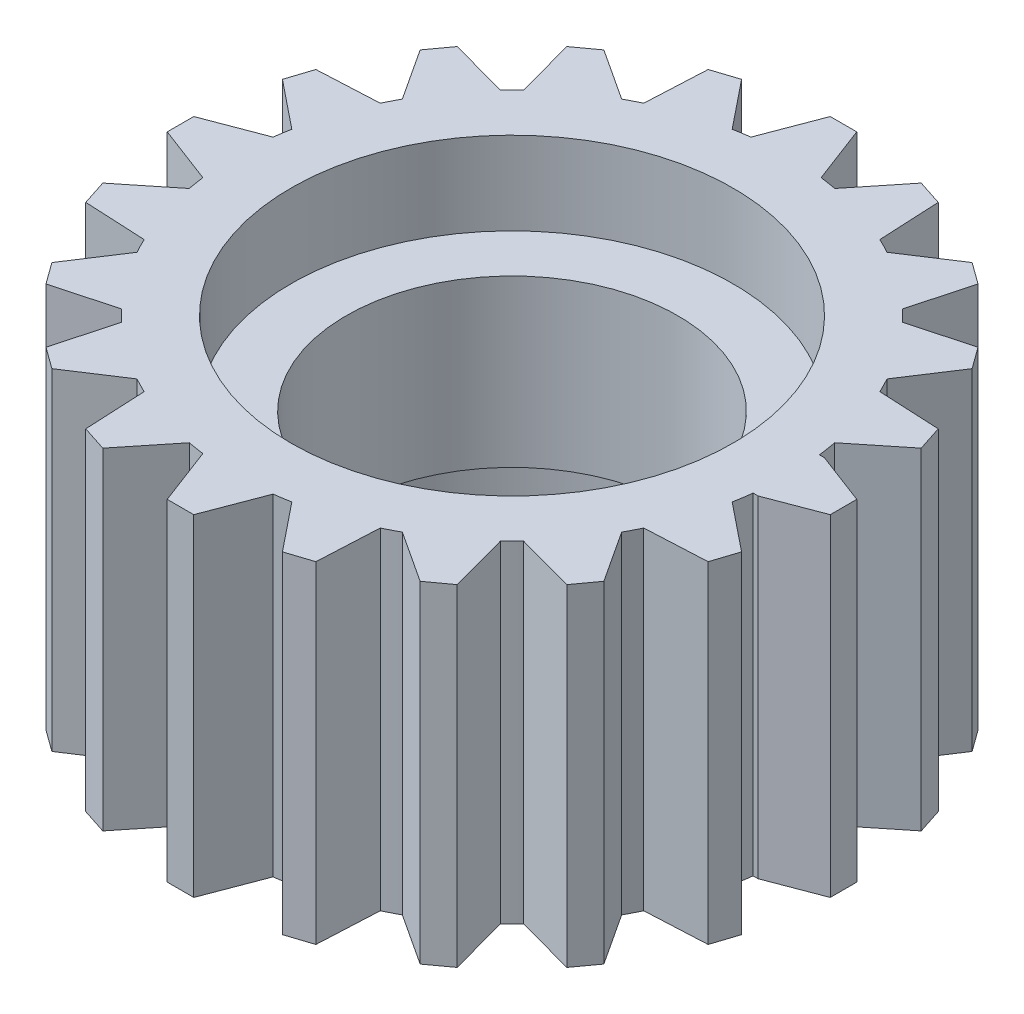
SolidWorks part; units mm, degrees
ref_plane "Front Plane" through (0, 0, 0) normal (0, 0, 1) x (1, 0, 0)
ref_plane "Top Plane" through (0, 0, 0) normal (0, 1, 0) x (1, 0, 0)
ref_plane "Right Plane" through (0, 0, 0) normal (1, 0, 0) x (0, 0, -1)
sketch "Sketch2" plane through (0, 0, 0) normal (0, 1, 0) x (1, 0, 0)
  line L0 (0, 0) -> (39.7409, 0) construction
  line L2 (0, 35.6097) -> (0, 0) construction
  line L3 (0, -3) -> (39.7409, -3)
  line L4 (0, 3) -> (39.7409, 3)
  line L5 (30, 1.2) -> (30, -1.2)
  line L6 (30, -1.2) -> (24.7972, -3.1775)
  line L7 (30, 1.2) -> (24.7972, 3.1775)
  line L8 (28.9025, -8.1292) -> (24.5655, -4.6408)
  line L9 (28.1609, -10.4118) -> (22.6017, -10.6848)
  line L10 (28.9025, -8.1292) -> (28.1609, -10.4118)
  line L11 (24.9759, -16.6627) -> (21.9291, -12.0048)
  line L12 (23.5652, -18.6044) -> (18.1937, -17.1461)
  line L13 (24.9759, -16.6627) -> (23.5652, -18.6044)
  line L14 (18.6044, -23.5652) -> (17.1461, -18.1937)
  line L15 (16.6627, -24.9759) -> (12.0048, -21.9291)
  line L16 (18.6044, -23.5652) -> (16.6627, -24.9759)
  line L17 (10.4118, -28.1609) -> (10.6848, -22.6017)
  line L18 (8.1292, -28.9025) -> (4.6408, -24.5655)
  line L19 (10.4118, -28.1609) -> (8.1292, -28.9025)
  line L20 (1.2, -30) -> (3.1775, -24.7972)
  line L21 (-1.2, -30) -> (-3.1775, -24.7972)
  line L22 (1.2, -30) -> (-1.2, -30)
  line L23 (-8.1292, -28.9025) -> (-4.6408, -24.5655)
  line L24 (-10.4118, -28.1609) -> (-10.6848, -22.6017)
  line L25 (-8.1292, -28.9025) -> (-10.4118, -28.1609)
  line L26 (-16.6627, -24.9759) -> (-12.0048, -21.9291)
  line L27 (-18.6044, -23.5652) -> (-17.1461, -18.1937)
  line L28 (-16.6627, -24.9759) -> (-18.6044, -23.5652)
  line L29 (-23.5652, -18.6044) -> (-18.1937, -17.1461)
  line L30 (-24.9759, -16.6627) -> (-21.9291, -12.0048)
  line L31 (-23.5652, -18.6044) -> (-24.9759, -16.6627)
  line L32 (-28.1609, -10.4118) -> (-22.6017, -10.6848)
  line L33 (-28.9025, -8.1292) -> (-24.5655, -4.6408)
  line L34 (-28.1609, -10.4118) -> (-28.9025, -8.1292)
  line L35 (-30, -1.2) -> (-24.7972, -3.1775)
  line L36 (-30, 1.2) -> (-24.7972, 3.1775)
  line L37 (-30, -1.2) -> (-30, 1.2)
  line L38 (-28.9025, 8.1292) -> (-24.5655, 4.6408)
  line L39 (-28.1609, 10.4118) -> (-22.6017, 10.6848)
  line L40 (-28.9025, 8.1292) -> (-28.1609, 10.4118)
  line L41 (-24.9759, 16.6627) -> (-21.9291, 12.0048)
  line L42 (-23.5652, 18.6044) -> (-18.1937, 17.1461)
  line L43 (-24.9759, 16.6627) -> (-23.5652, 18.6044)
  line L44 (-18.6044, 23.5652) -> (-17.1461, 18.1937)
  line L45 (-16.6627, 24.9759) -> (-12.0048, 21.9291)
  line L46 (-18.6044, 23.5652) -> (-16.6627, 24.9759)
  line L47 (-10.4118, 28.1609) -> (-10.6848, 22.6017)
  line L48 (-8.1292, 28.9025) -> (-4.6408, 24.5655)
  line L49 (-10.4118, 28.1609) -> (-8.1292, 28.9025)
  line L50 (-1.2, 30) -> (-3.1775, 24.7972)
  line L51 (1.2, 30) -> (3.1775, 24.7972)
  line L52 (-1.2, 30) -> (1.2, 30)
  line L53 (8.1292, 28.9025) -> (4.6408, 24.5655)
  line L54 (10.4118, 28.1609) -> (10.6848, 22.6017)
  line L55 (8.1292, 28.9025) -> (10.4118, 28.1609)
  line L56 (16.6627, 24.9759) -> (12.0048, 21.9291)
  line L57 (18.6044, 23.5652) -> (17.1461, 18.1937)
  line L58 (16.6627, 24.9759) -> (18.6044, 23.5652)
  line L59 (23.5652, 18.6044) -> (18.1937, 17.1461)
  line L60 (24.9759, 16.6627) -> (21.9291, 12.0048)
  line L61 (23.5652, 18.6044) -> (24.9759, 16.6627)
  line L62 (28.1609, 10.4118) -> (22.6017, 10.6848)
  line L63 (28.9025, 8.1292) -> (24.5655, 4.6408)
  line L64 (28.1609, 10.4118) -> (28.9025, 8.1292)
  circle A0 centre (0, 0) radius 15
  circle A1 centre (0, 0) radius 20
  circle A3 centre (0, 0) radius 25
  point P16 (30, 0)
  point P17 (0, 0)
  point P94 (0, 0)
  dimension "D1" = 3
  dimension "D3" = 20
  dimension "D2" = 6
extrude "Boss-Extrude1" add sketch "Sketch2" along normal blind 30 contours A3 L3 A1 L4 | L4 A1 L3 A0 | A3 L42 L43 L41 | A3 L39 L40 L38 | A3 L36 L37 L35 | A3 L33 L34 L32 | A3 L30 L31 L29 | A3 L27 L28 L26 | A3 L24 L25 L23 | A3 L21 L22 L20 | A3 L18 L19 L17 | A3 L15 L16 L14 | A3 L12 L13 L11 | A3 L9 L10 L8 | A3 L3 L6 L5 L7 L4 | A3 L63 L64 L62 | A3 L60 L61 L59 | A3 L57 L58 L56 | A3 L54 L55 L53 | A3 L51 L52 L50 | A3 L48 L49 L47 | A3 L45 L46 L44 | L3 A1 L4 A0 | L3 A3 L4 A1 region at (17.4117, 0, 0) region at (17.2353, 0, 3.5641) region at (22.4321, 0, 0) region at (22.2965, 0, 3.7058) region at (27.0981, 0, 0) region at (25.7645, 0, 8.3714) region at (25.7645, 0, -8.3714) region at (21.9166, 0, 15.9233) region at (21.9166, 0, -15.9233) region at (15.9233, 0, 21.9166) region at (15.9233, 0, -21.9166) region at (8.3714, 0, 25.7645) region at (8.3714, 0, -25.7645) region at (0, 0, 27.0904) region at (0, 0, -27.0904) region at (-8.3714, 0, 25.7645) region at (-8.3714, 0, -25.7645) region at (-15.9233, 0, 21.9166) region at (-15.9233, 0, -21.9166) region at (-21.9166, 0, 15.9233) region at (-21.9166, 0, -15.9233) region at (-25.7645, 0, 8.3714) region at (-25.7645, 0, -8.3714) region at (-27.0904, 0, 0)
sketch "Sketch6" plane through (0, 30, 0) normal (0, 1, 0) x (1, 0, 0)
  circle A0 centre (0, 0) radius 20
extrude "Cut-Extrude2" cut sketch "Sketch6" against normal blind 7.5
extrude "Cut-Extrude3" cut sketch "Sketch6<2>" against normal blind 7.5 from offset 22.5 offset against normal yes
sketch "Sketch6<2>" plane through (0, 30, 0) normal (0, 1, 0) x (1, 0, 0) same geometry as "Sketch6"
